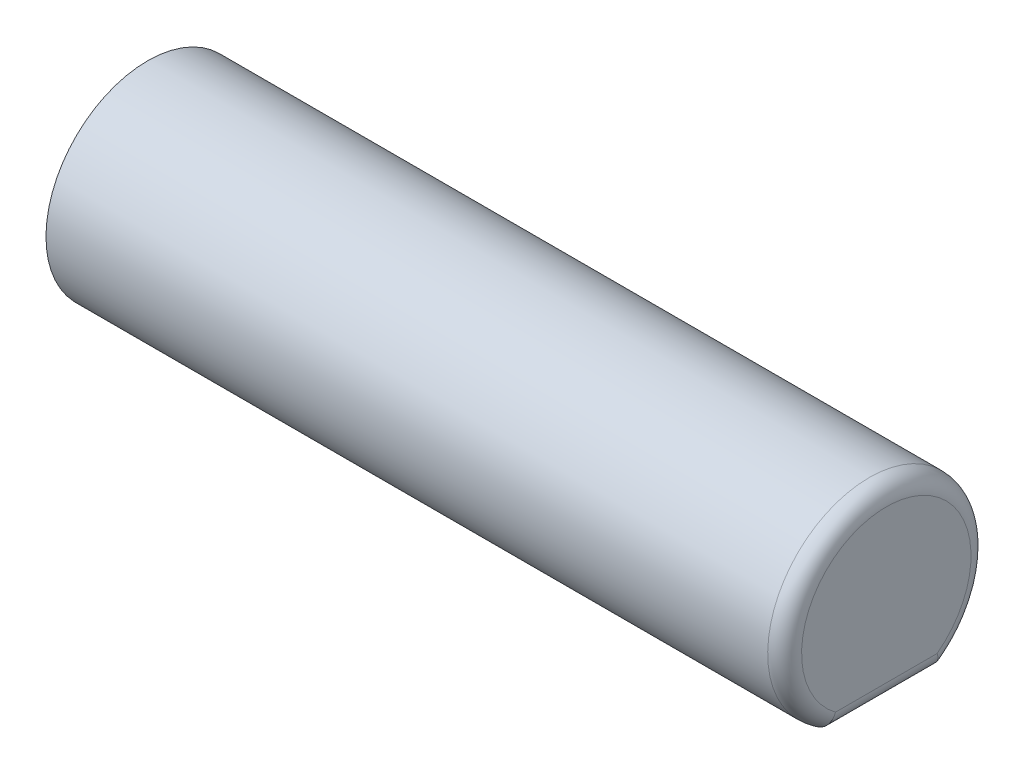
SolidWorks part; units mm, degrees
ref_plane "Front Plane" through (0, 0, 0) normal (0, 0, 1) x (1, 0, 0)
ref_plane "Top Plane" through (0, 0, 0) normal (0, 1, 0) x (1, 0, 0)
ref_plane "Right Plane" through (0, 0, 0) normal (1, 0, 0) x (0, 0, -1)
sketch "Sketch1" plane through (0, 0, 0) normal (1, 0, 0) x (0, 0, -1)
  circle A0 centre (0, 0) radius 3
extrude "Boss-Extrude1" add sketch "Sketch1" along normal blind 21.8
sketch "Sketch2" plane through (21.8, 0, 0) normal (1, 0, 0) x (0, 0, -1)
  line L0 (0, 0) -> (0, -2.5) construction
  line L1 (0, -2.5) -> (-1.6583, -2.5)
  line L2 (0, -2.5) -> (1.6583, -2.5)
  circle A0 centre (0, 0) radius 3 construction
  arc A1 (-1.6583, -2.5) -> (1.6583, -2.5) centre (0, 0) ccw
extrude "Cut-Extrude2" cut sketch "Sketch2" against normal blind 12
fillet "Fillet1" radius 0.5 2 edges at (21.8, 3, 0) (21.8, -2.5, 0)
